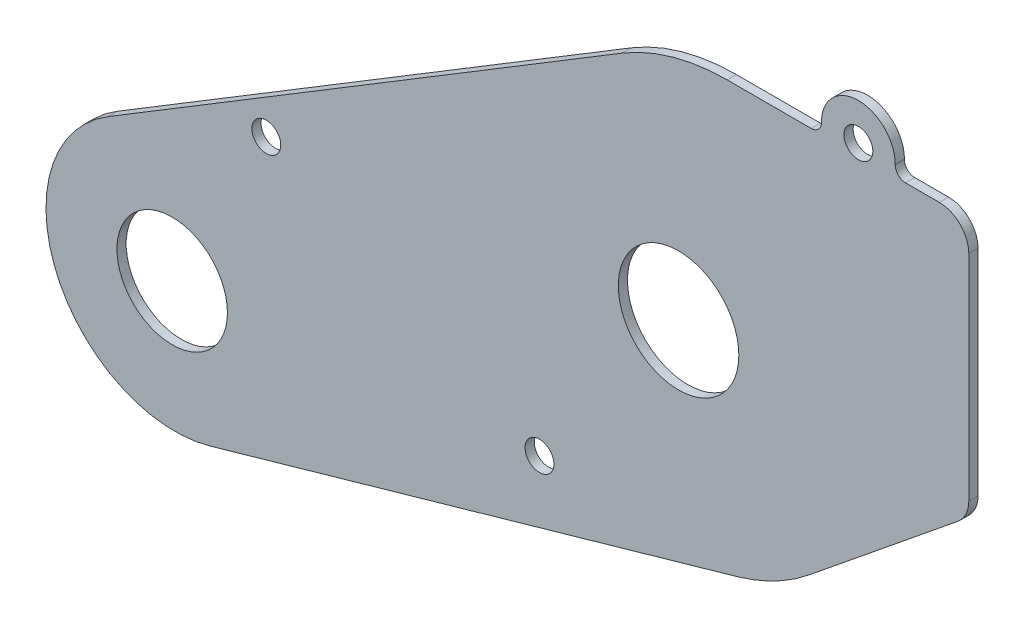
SolidWorks part; units mm, degrees
material "ABS PC"
ref_plane "Front Plane" through (0, 0, 0) normal (0, 0, 1) x (1, 0, 0)
ref_plane "Top Plane" through (0, 0, 0) normal (0, 1, 0) x (1, 0, 0)
ref_plane "Right Plane" through (0, 0, 0) normal (1, 0, 0) x (0, 0, -1)
sketch "Sketch2" plane through (0, 0, 0) normal (0, 0, 1) x (1, 0, 0)
  line L0 (25.0911, -52.0924) -> (-65.6838, -78.0001)
  line L1 (-83.3142, -37.6288) -> (5.2713, 16.1338)
  line L2 (52.3571, 23.0853) -> (52.3571, 22.9801)
  line L3 (-85.0103, -69.3804) -> (-59.5064, -43.8765) construction
  line L5 (63.1592, -24.8058) -> (37.5195, -45.6224)
  line L7 (39.6571, 23.0853) -> (39.6571, 22.9801)
  line L8 (54.1351, 21.2021) -> (59.9573, 21.2021)
  line L10 (65.831, 16.0128) -> (55.9968, 5.3253) construction
  line L11 (42.2751, -9.5867) -> (65.831, 16.0128) construction
  line L12 (65.831, 16.0128) -> (65.831, 22.3102) construction
  line L14 (37.8791, 21.2021) -> (23.3913, 21.2021)
  line L15 (65.0373, 16.1221) -> (65.0373, -20.8619)
  arc A3 (37.5195, -45.6224) -> (25.0911, -52.0924) centre (15.506, -18.5085) cw
  arc A4 (-83.3142, -37.6288) -> (-65.6838, -78.0001) centre (-71.7833, -56.6285) ccw
  circle A8 centre (15.0168, -18.8831) radius 10.3877
  circle A9 centre (-72.2583, -56.6285) radius 9.525
  arc A12 (59.9573, 21.2021) -> (65.0373, 16.1221) centre (59.9573, 16.1221) cw
  arc A13 (63.1592, -24.8058) -> (65.0373, -20.8619) centre (59.9573, -20.8619) ccw
  arc A14 (5.2713, 16.1338) -> (23.3913, 21.2021) centre (23.3913, -13.7229) cw
  arc A16 (52.3571, 23.0853) -> (39.6571, 23.0853) centre (46.0071, 23.0853) ccw
  arc A17 (52.3571, 22.9801) -> (54.1351, 21.2021) centre (54.1351, 22.9801) ccw
  arc A18 (39.6571, 22.9801) -> (37.8791, 21.2021) centre (37.8791, 22.9801) cw
  point P19 (-72.2583, -56.6285)
  point P20 (15.506, -18.5085)
  point P36 (52.3571, 21.2021)
  dimension "D1" = 5.08
  dimension "D2" = 5.08
  dimension "D4" = 1.778
  dimension "D3" = 34.925
extrude "Boss-Extrude1" add sketch "Sketch2" along normal blind 1.5875
sketch "Sketch4" plane through (0, 0, 1.5875) normal (0, 0, 1) x (1, 0, 0)
  line L0 (-58.677, -22.6764) -> (-56.0414, -27.0192) construction
  line L1 (5.2713, 16.1338) -> (-83.3142, -37.6288) construction
  line L2 (-6.9135, -55.744) -> (-8.9513, -51.0906) construction
  line L3 (-62.0382, -79.8833) -> (25.1671, -41.6958) construction
  circle A1 centre (-56.0414, -27.0192) radius 3.9687 construction
  circle A2 centre (-8.9513, -51.0906) radius 3.9688 construction
  point P15 (46.0071, 23.0853)
  point P16 (0, 0)
hole_wizard "#10 Clearance Hole1" positions "Sketch5" profile "Sketch6" hole size "#10" standard "ANSI Inch" end condition through all
sketch "Sketch5" plane through (0, 0, 1.5875) normal (0, 0, 1) x (1, 0, 0)
  point P0 (-56.0414, -27.0192)
  point P3 (-8.9513, -51.0906)
  point P6 (46.0071, 23.0853)
  point P10 (46.0071, 23.0853)
sketch "Sketch6" plane through (-56.0414, -27.0192, 1.5875) normal (1, 0, 0) x (0, -1, 0)
  line L0 (0, 0) -> (0, 1.5875)
  line L1 (0, 1.5875) -> (2.4892, 1.5875)
  line L2 (2.4892, 1.5875) -> (2.4892, 0)
  line L5 (2.4892, 0) -> (0, 0)
  line L11 (0, -6.35) -> (0, 107.95) construction
  dimension "Thru Hole Dia." = 4.9784
  dimension "Thru Hole Depth" = 1.5875
